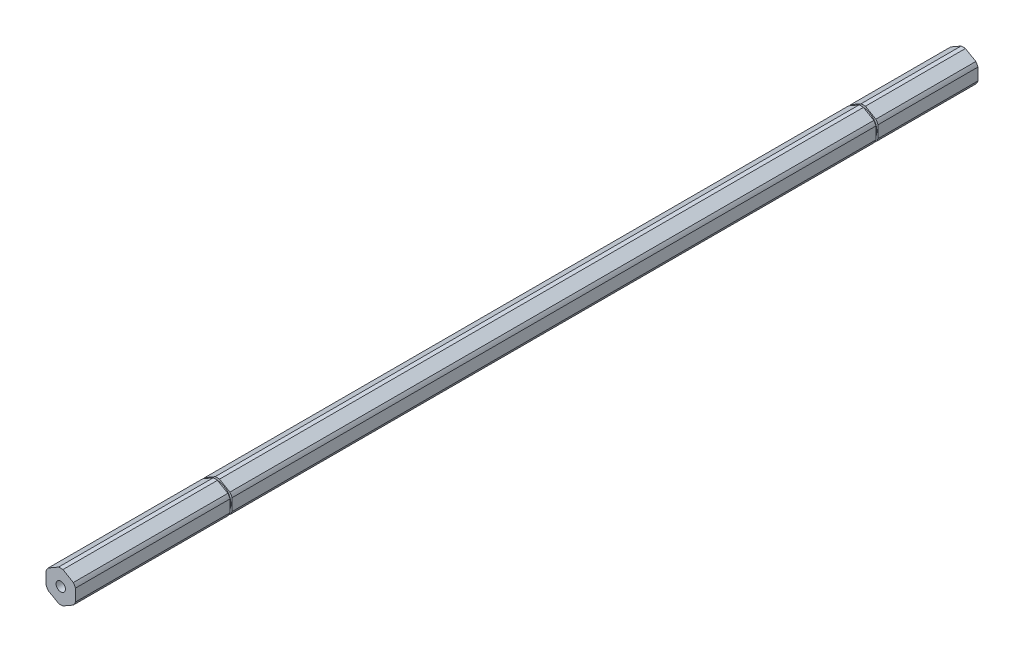
SolidWorks part; units mm, degrees
material "6061-T6 (SS)"
ref_plane "Front Plane" through (0, 0, 0) normal (0, 0, 1) x (1, 0, 0)
ref_plane "Top Plane" through (0, 0, 0) normal (0, 1, 0) x (1, 0, 0)
ref_plane "Right Plane" through (0, 0, 0) normal (1, 0, 0) x (0, 0, -1)
sketch "Sketch1" plane through (0, 0, 0) normal (0, 0, 1) x (1, 0, 0)
  line L1 (0, 7.3323) -> (-6.35, 3.6662)
  line L2 (-6.35, 3.6662) -> (-6.35, -3.6662)
  line L3 (-6.35, -3.6662) -> (0, -7.3323)
  line L4 (0, -7.3323) -> (6.35, -3.6662)
  line L5 (6.35, -3.6662) -> (6.35, 3.6662)
  line L6 (6.35, 3.6662) -> (0, 7.3323)
  circle A0 centre (0, 0) radius 6.35 construction
  circle A1 centre (0, 0) radius 6.858
  dimension "D1" = 12.7
  dimension "D2" = 13.716
extrude "Boss-Extrude1" add sketch "Sketch1" along normal mid plane 388.6403 contours L5 A1 L6 L1 L2 L3 L4 region at (0, 0, 0)
sketch "Sketch2" plane through (0, 0, 194.3202) normal (0, 0, 1) x (1, 0, 0)
  circle A0 centre (0, 0) radius 2.0193
  dimension "D1" = 4.0386
extrude "Cut-Extrude1" cut sketch "Sketch2" against normal through all
sketch "Sketch4" plane through (0, 0, 0) normal (0, 1, 0) x (1, 0, 0)
  line L0 (-2.0193, -194.3202) -> (2.0193, -194.3202) construction
  line L5 (-0.9317, -194.3202) -> (0.9317, -194.3202) construction
  line L7 (9.0297, 151.2672) -> (5.8547, 151.2672)
  line L8 (9.0297, 151.2672) -> (9.0297, 150.3782)
  line L9 (9.0297, 150.3782) -> (5.8547, 150.3782)
  line L10 (5.8547, 151.2672) -> (5.8547, 150.3782)
  line L11 (5.8547, -127.7722) -> (9.0297, -127.7722)
  line L12 (0, 194.3202) -> (0, -194.3202) construction
  line L13 (2.0193, 194.3202) -> (-2.0193, 194.3202) construction
  line L14 (5.8547, -127.7722) -> (5.8547, -126.8832)
  line L15 (5.8547, -126.8832) -> (9.0297, -126.8832)
  line L16 (9.0297, -127.7722) -> (9.0297, -126.8832)
  dimension "D1" = 0.889
  dimension "D2" = 388.6403
  dimension "D3" = 5.8547
  dimension "D4" = 43.053
  dimension "D5" = 3.175
  dimension "D6" = 3.175
  dimension "D7" = 0.889
  dimension "D8" = 66.548
revolve "Cut-Revolve4" cut sketch "Sketch4" angle 360 about L12
hole_wizard "#10-32 Tapped Hole1" positions "3DSketch1" profile "Sketch5" tap size "#10-32" standard "ANSI Inch"
sketch3d "3DSketch1"
  line L0 (0, 0, -151.2672) -> (0, 0, -194.3202) construction
  point P0 (0, 0, 194.3202)
sketch "Sketch5" plane through (0, 0, 194.3202) normal (1, 0, 0) x (0, -1, 0)
  line L0 (0, 0) -> (0, 13.1513)
  line L1 (0, 13.1513) -> (2.0193, 11.938)
  line L2 (2.0193, 11.938) -> (2.0193, 0)
  line L5 (2.0193, 0) -> (0, 0)
  line L10 (0, 13.1513) -> (-2.0193, 11.938) construction
  line L11 (0, -6.35) -> (0, 107.95) construction
  dimension "Tap Drill Dia." = 4.0386
  dimension "Tap Drill Depth" = 11.938
  dimension "Drill Angle" = 118
cosmetic thread "Hole Thread1" parameters "D1"=9.652, "D2"=4.826
equation "\"D1@Boss-Extrude1\"=14.25"
